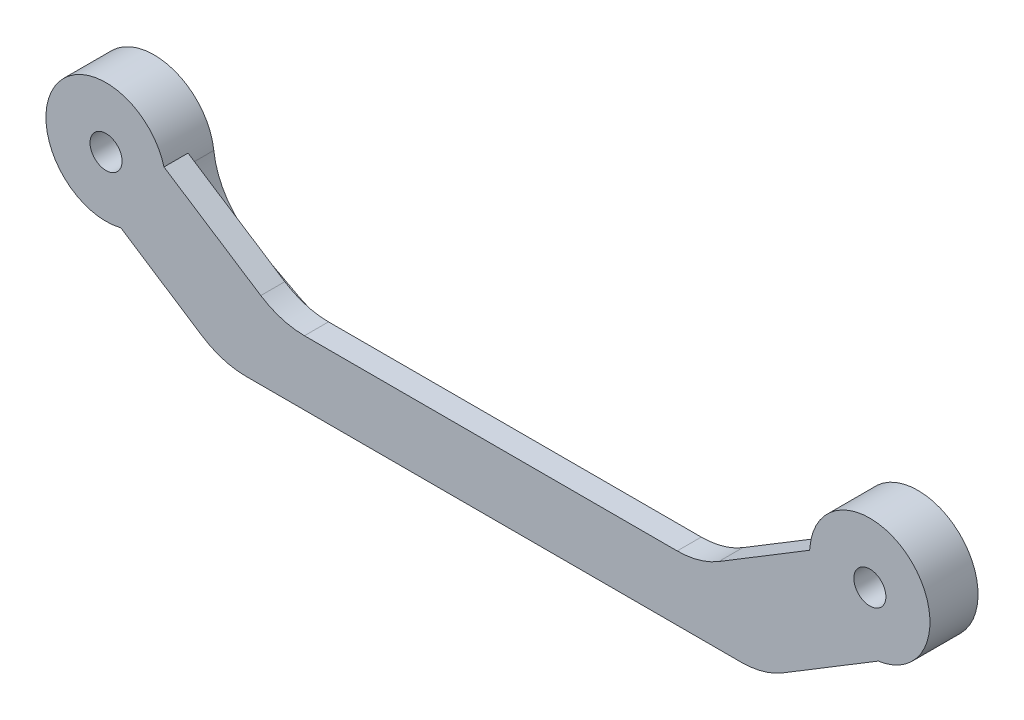
SolidWorks part; units mm, degrees
ref_plane "前视基准面" through (0, 0, 0) normal (0, 0, 1) x (1, 0, 0)
ref_plane "上视基准面" through (0, 0, 0) normal (0, 1, 0) x (1, 0, 0)
ref_plane "右视基准面" through (0, 0, 0) normal (1, 0, 0) x (0, 0, -1)
other "Configuration Table"
sketch "草图1" plane through (0, 0, 0) normal (0, 0, 1) x (1, 0, 0)
  line L0 (7.2299, 1.9945) -> (21.7939, -7.4752)
  line L1 (21.7939, -7.4752) -> (74.0668, -7.4752)
  line L2 (74.0668, -7.4752) -> (87.813, 0.8723)
  line L3 (1.8412, -7.2705) -> (14.4869, -15.5109)
  line L4 (14.4869, -15.5109) -> (82.0683, -15.5109)
  line L5 (82.0683, -15.5109) -> (96.3583, -6.8332)
  circle A0 centre (0, 0) radius 7.5
  circle A1 centre (95.3078, 0.5929) radius 7.5
  point P9 (0, 0)
  point P12 (0, 0)
  point P13 (0, 0)
  point P14 (0, 0)
  point P15 (0, 0)
  point P16 (0, 0)
  point P17 (0, 0)
  point P18 (0, 0)
  dimension "D1" = 15
  dimension "D2" = 15
extrude "凸台-拉伸1" add sketch "草图1" along normal blind 3 contours A0 | A1 L2 L1 L0 A0 L3 L4 L5 | A1 L5
sketch "草图2" plane through (0, 0, 3) normal (0, 0, 1) x (1, 0, 0)
  circle A0 centre (0, 0) radius 2
  circle A1 centre (95.3078, 0.5929) radius 2
  dimension "D1" = 4
  dimension "D2" = 4
extrude "切除-拉伸1" cut sketch "草图2" against normal through all
sketch "草图3" plane through (0, 0, 0) normal (0, 0, -1) x (-1, 0, 0)
  line L0 (-88.7705, -3.0833) -> (-75.0514, -10.7982)
  line L1 (-75.0514, -10.7982) -> (-20.3236, -10.7982)
  line L2 (-20.3236, -10.7982) -> (-6.6232, -3.519)
  line L4 (-4.4753, -6.0185) -> (-18.8151, -13.6374)
  line L5 (-18.8151, -13.6374) -> (-76.6481, -13.6374)
  line L6 (-76.6481, -13.6374) -> (-91.0159, -5.5577)
  circle A0 centre (-95.3078, 0.5929) radius 7.5
  circle A1 centre (0, 0) radius 7.5
  circle M2 centre (0, 0) radius 2
  circle M3 centre (-95.3078, 0.5929) radius 2
  arc M4 (-1.8412, -7.2705) -> (-7.2299, 1.9945) centre (0, 0) ccw
  arc M8 (-87.813, 0.8723) -> (-96.3583, -6.8332) centre (-95.3078, 0.5929) ccw
extrude "凸台-拉伸9" add sketch "草图3" along normal blind 3 contours A0 M8 M3 | A1 L2 L1 L0 A0 L6 L5 L4 | A1 M4 M2
fillet "圆角1" radius 10 6 edges at (87.813, 0.8723, 1.5) (1.8412, -7.2705, 1.5) (88.7705, -3.0833, -1.5) (91.0159, -5.5577, -1.5) (4.4753, -6.0185, -1.5) (6.6232, -3.519, -1.5)
fillet "圆角2" radius 10 8 edges at (14.4869, -15.5109, 1.5) (82.0683, -15.5109, 1.5) (76.6481, -13.6374, -1.5) (18.8151, -13.6374, -1.5) (20.3236, -10.7982, -1.5) (21.7939, -7.4752, 1.5) (74.0668, -7.4752, 1.5) (75.0514, -10.7982, -1.5)
